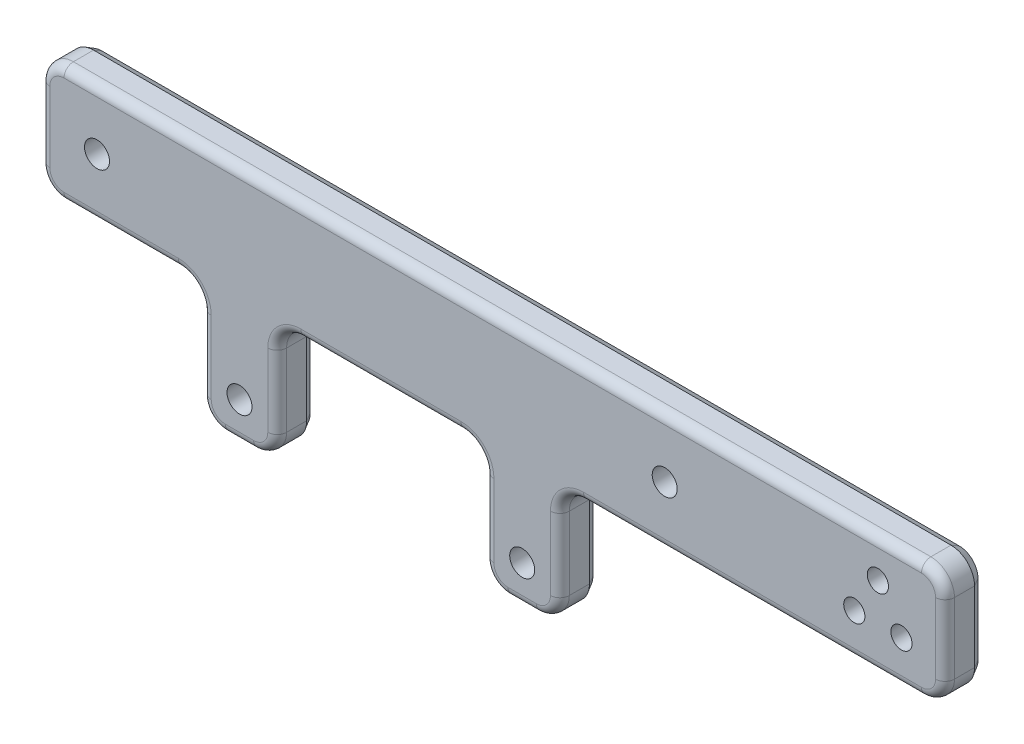
SolidWorks part; units mm, degrees
note: '?' marks a value the reader was unsure of.
ref_plane "Front Plane" through (0, 0, 0) normal (0, 0, 1) x (1, 0, 0)
ref_plane "Top Plane" through (0, 0, 0) normal (0, 1, 0) x (1, 0, 0)
ref_plane "Right Plane" through (0, 0, 0) normal (1, 0, 0) x (0, 0, -1)
sketch "Sketch2" plane through (0, 0, 0) normal (0, 0, 1) x (1, 0, 0)
  line L1 (-96, -12.5) -> (96, -12.5)
  line L2 (-96, -12.5) -> (-96, 12.5)
  line L3 (-96, 12.5) -> (96, 12.5)
  line L4 (96, -12.5) -> (96, 12.5)
  line L5 (-96, -12.5) -> (96, 12.5) construction
  line L6 (-96, 12.5) -> (96, -12.5) construction
  point P0 (0, 0)
  dimension "D1" = 192
  dimension "D2" = 25
extrude "Boss-Extrude1" add sketch "Sketch2" along normal blind 8
sketch "Sketch3" plane through (0, 0, 8) normal (0, 0, 1) x (1, 0, 0)
  line L0 (-96, 12.5) -> (-96, -12.5) construction
  line L4 (86.75, -3.5) -> (76.75, -3.5) construction
  line L5 (81.75, 4.5) -> (81.75, -3.5) construction
  line L8 (96, 12.5) -> (-96, 12.5) construction
  circle A0 centre (-84, 0) radius 2.65
  circle A1 centre (36.5, 0) radius 2.65
  circle A2 centre (76.75, -3.5) radius 2.25
  circle A3 centre (86.75, -3.5) radius 2.25
  circle A4 centre (81.75, 4.5) radius 2.25
  point P10 (0, 0)
  point P11 (-96, 0)
  dimension "D1" = 5.3
  dimension "D10" = 4.5
  dimension "D3" = 12
  dimension "D4" = 120.5
  dimension "D5" = 8
  dimension "D7" = 8
  dimension "D8" = 10
  dimension "D9" = 165.75
extrude "Cut-Extrude1" cut sketch "Sketch3" against normal through all
sketch "Sketch5" plane through (0, 0, 8) normal (0, 0, 1) x (1, 0, 0)
  line L0 (-96, -12.5) -> (96, -12.5) construction
  line L1 (-61.75, -12.5) -> (-45.75, -12.5)
  line L2 (-61.75, -12.5) -> (-61.75, -38)
  line L3 (-61.75, -38) -> (-45.75, -38)
  line L4 (-45.75, -12.5) -> (-45.75, -38)
  line L5 (36.5, 0) -> (-84, 0) construction
  line L10 (-23.75, 0) -> (-23.75, -29.3478) construction
  line L11 (14.25, -38) -> (-1.75, -38)
  line L12 (-1.75, -12.5) -> (-1.75, -38)
  line L13 (14.25, -12.5) -> (-1.75, -12.5)
  line L14 (14.25, -12.5) -> (14.25, -38)
  circle A0 centre (-53.75, -30) radius 2.65
  circle A1 centre (-84, 0) radius 2.65 construction
  circle A2 centre (6.25, -30) radius 2.65
  point P8 (0, 0)
  point P9 (-53.75, -38)
  point P15 (-23.75, 0)
  dimension "D1" = 30
  dimension "D2" = 8
  dimension "D3" = 16
  dimension "D4" = 30
extrude "Boss-Extrude2" add sketch "Sketch5" against normal up to surface (8 mm away) up to face at (-81.35, 0, 0)
fillet "Fillet1" radius 5 12 edges at (-96, -12.5, 4) (-96, 12.5, 4) (96, -12.5, 4) (96, 12.5, 4) (14.25, -12.5, 4) (14.25, -38, 4) (-1.75, -38, 4) (-1.75, -12.5, 4) (-61.75, -12.5, 4) (-45.75, -12.5, 4) (-61.75, -38, 4) (-45.75, -38, 4)
fillet "Fillet2" radius 2 24 edges at (94.5355, 11.0355, 8) (96, 0, 8) (94.5355, -11.0355, 8) (55.125, -12.5, 8) (-78.875, -12.5, 8) (-94.5355, -11.0355, 8) (-96, 0, 8) (-94.5355, 11.0355, 8) (0, 12.5, 8) (15.7145, -13.9645, 8) (14.25, -25.25, 8) (12.7855, -36.5355, 8) (6.25, -38, 8) (-0.2855, -36.5355, 8) (-1.75, -25.25, 8) (-3.2145, -13.9645, 8) (-23.75, -12.5, 8) (-44.2855, -13.9645, 8) (-45.75, -25.25, 8) (-47.2145, -36.5355, 8) (-53.75, -38, 8) (-60.2855, -36.5355, 8) (-61.75, -25.25, 8) (-63.2145, -13.9645, 8)
chamfer "Chamfer1" distance 1 angle 60 24 edges at (0, 12.5, 0) (-94.5355, 11.0355, 0) (94.5355, 11.0355, 0) (-96, 0, 0) (96, 0, 0) (-94.5355, -11.0355, 0) (94.5355, -11.0355, 0) (-78.875, -12.5, 0) (55.125, -12.5, 0) (6.25, -38, 0) (12.7855, -36.5355, 0) (-0.2855, -36.5355, 0) (14.25, -25.25, 0) (-1.75, -25.25, 0) (15.7145, -13.9645, 0) (-3.2145, -13.9645, 0) (-23.75, -12.5, 0) (-44.2855, -13.9645, 0) (-45.75, -25.25, 0) (-47.2145, -36.5355, 0) (-53.75, -38, 0) (-60.2855, -36.5355, 0) (-61.75, -25.25, 0) (-63.2145, -13.9645, 0)
chamfer "Chamfer2" distance 1 angle 30 7 edges at (89, -3.5, 0) (84, 4.5, 0) (79, -3.5, 0) (39.15, 0, 0) (-81.35, 0, 0) (-56.4, -30, 0) (3.6, -30, 0)
ref_axis "Axis1" through (-53.75, -30, 1) along (0, 0, 1)?
ref_axis "Axis2" through (6.25, -30, 1) along (0, 0, 1)?
ref_plane "Plane1" through (6.25, 0, 0) normal (1, 0, 0) x (0, 0, -1)
ref_plane "Plane2" through (-53.75, 0, 0) normal (1, 0, 0) x (0, 0, -1)
ref_plane "Plane3" through (-23.75, 0, 0) normal (1, 0, 0) x (0, 0, -1)
